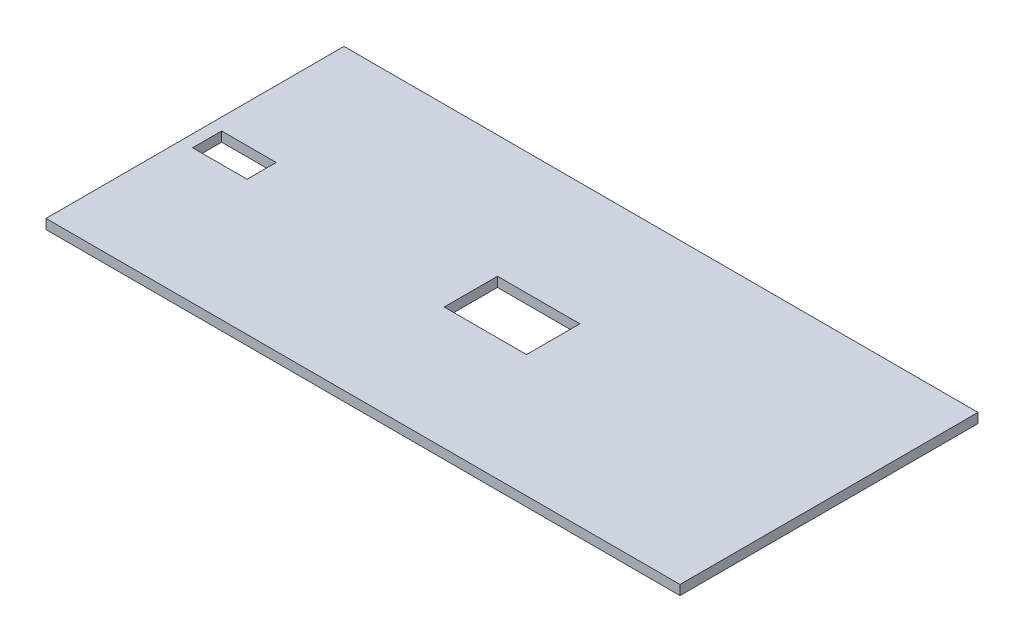
SolidWorks part; units mm, degrees
ref_plane "Front Plane" through (0, 0, 0) normal (0, 0, 1) x (1, 0, 0)
ref_plane "Top Plane" through (0, 0, 0) normal (0, 1, 0) x (1, 0, 0)
ref_plane "Right Plane" through (0, 0, 0) normal (1, 0, 0) x (0, 0, -1)
sketch "Sketch1" plane through (0, 0, 0) normal (0, 1, 0) x (1, 0, 0)
  line L0 (81.2702, 169.2523) -> (342.9702, 169.2523)
  line L1 (81.2702, 189.2523) -> (342.9702, 189.2523)
  line L2 (81.2702, 189.2523) -> (81.2702, 66.2523)
  line L3 (81.2702, 66.2523) -> (342.9702, 66.2523)
  line L4 (342.9702, 189.2523) -> (342.9702, 66.2523)
  line L5 (81.2702, 86.2523) -> (342.9702, 86.2523)
  line L6 (114.7702, 189.2523) -> (114.7702, 66.2523)
  line L7 (309.4702, 189.2523) -> (309.4702, 66.2523)
  line L8 (178.6202, 189.2523) -> (178.6202, 66.2523)
  line L9 (245.6202, 189.2523) -> (245.6202, 66.2523)
  line L10 (188.6202, 189.2523) -> (188.6202, 66.2523)
  line L11 (235.6202, 189.2523) -> (235.6202, 66.2523)
  dimension "D1" = 20
  dimension "D2" = 20
  dimension "D3" = 83
  dimension "D4" = 33.5
  dimension "D5" = 33.5
  dimension "D6" = 63.85
  dimension "D7" = 63.85
  dimension "D8" = 47
  dimension "D9" = 10
  dimension "D10" = 10
  dimension "L_base" = 261.7
  dimension "W_base" = 123
extrude "Boss-Extrude7" add sketch "Sketch1" along normal blind 4 contours L6 L5 L2 L3 | L8 L5 L6 L3 | L10 L5 L8 L3 | L11 L5 L10 L3 | L5 L11 L3 L9 | L5 L9 L3 L7 | L5 L7 L3 L4 | L0 L7 L5 L4 | L0 L9 L5 L7 | L0 L11 L5 L9 | L11 L0 L10 L5 | L8 L0 L6 L5 | L6 L0 L2 L5 | L10 L0 L8 L5 | L6 L1 L2 L0 | L8 L1 L6 L0 | L10 L1 L8 L0 | L11 L1 L10 L0 | L1 L11 L0 L9 | L1 L9 L0 L7 | L1 L7 L0 L4 region at (98.0202, 0, -179.2523) region at (98.0202, 0, -127.7523) region at (146.6952, 0, -179.2523) region at (146.6952, 0, -127.7523) region at (98.0202, 0, -76.2523) region at (183.6202, 0, -179.2523) region at (183.6202, 0, -127.7523) region at (146.6952, 0, -76.2523) region at (212.1202, 0, -179.2523) region at (212.1202, 0, -127.7523) region at (183.6202, 0, -76.2523) region at (240.6202, 0, -179.2523) region at (240.6202, 0, -127.7523) region at (212.1202, 0, -76.2523) region at (277.5452, 0, -179.2523) region at (277.5452, 0, -127.7523) region at (240.6202, 0, -76.2523) region at (326.2202, 0, -179.2523) region at (326.2202, 0, -127.7523) region at (277.5452, 0, -76.2523) region at (326.2202, 0, -76.2523)
sketch "Sketch2" plane through (0, 4, 0) normal (0, 1, 0) x (1, 0, 0)
  line L0 (81.2702, 189.2523) -> (81.2702, 66.2523) construction
  line L1 (86.2702, 133.7523) -> (108.7702, 133.7523)
  line L2 (86.2702, 133.7523) -> (86.2702, 121.7523)
  line L3 (86.2702, 121.7523) -> (108.7702, 121.7523)
  line L4 (108.7702, 133.7523) -> (108.7702, 121.7523)
  line L6 (81.2702, 189.2523) -> (342.9702, 189.2523) construction
  point P8 (97.5202, 133.7523)
  dimension "D1" = 12
  dimension "D2" = 22.5
  dimension "D3" = 5
  dimension "D4" = 55.5
extrude "Cut-Extrude1" cut sketch "Sketch2" against normal blind 4
sketch "Sketch3" plane through (0, 4, 0) normal (0, 1, 0) x (1, 0, 0)
  line L0 (81.2702, 189.2523) -> (342.9702, 189.2523) construction
  line L1 (195.1202, 138.7523) -> (229.1202, 138.7523)
  line L2 (195.1202, 138.7523) -> (195.1202, 116.7523)
  line L3 (195.1202, 116.7523) -> (229.1202, 116.7523)
  line L4 (229.1202, 138.7523) -> (229.1202, 116.7523)
  line L5 (81.2702, 189.2523) -> (81.2702, 66.2523) construction
  dimension "W_TCS3200_Sensor" = 22
  dimension "L_TCS3200_Sensor" = 34
  dimension "D1" = 50.5
  dimension "D2" = 113.85
extrude "Cut-Extrude2" cut sketch "Sketch3" against normal blind 4 contours L4 L3 L2 L1
equation "\"D2@Sketch1\"=\"D1@Sketch1\""
equation "\"D5@Sketch1\"=\"D4@Sketch1\""
equation "\"D7@Sketch1\"=\"D6@Sketch1\""
equation "\"D10@Sketch1\"=\"D9@Sketch1\""
equation "\"D4@Sketch2\"=(\"D1@Sketch1\"*2+\"D3@Sketch1\")/2-\"D1@Sketch2\"/2"
equation "\"D1@Sketch3\"=\"W_base@Sketch1\"/2-\"W_TCS3200_Sensor@Sketch3\"/2"
equation "\"D2@Sketch3\"=\"L_base@Sketch1\"/2-\"L_TCS3200_Sensor@Sketch3\"/2"
